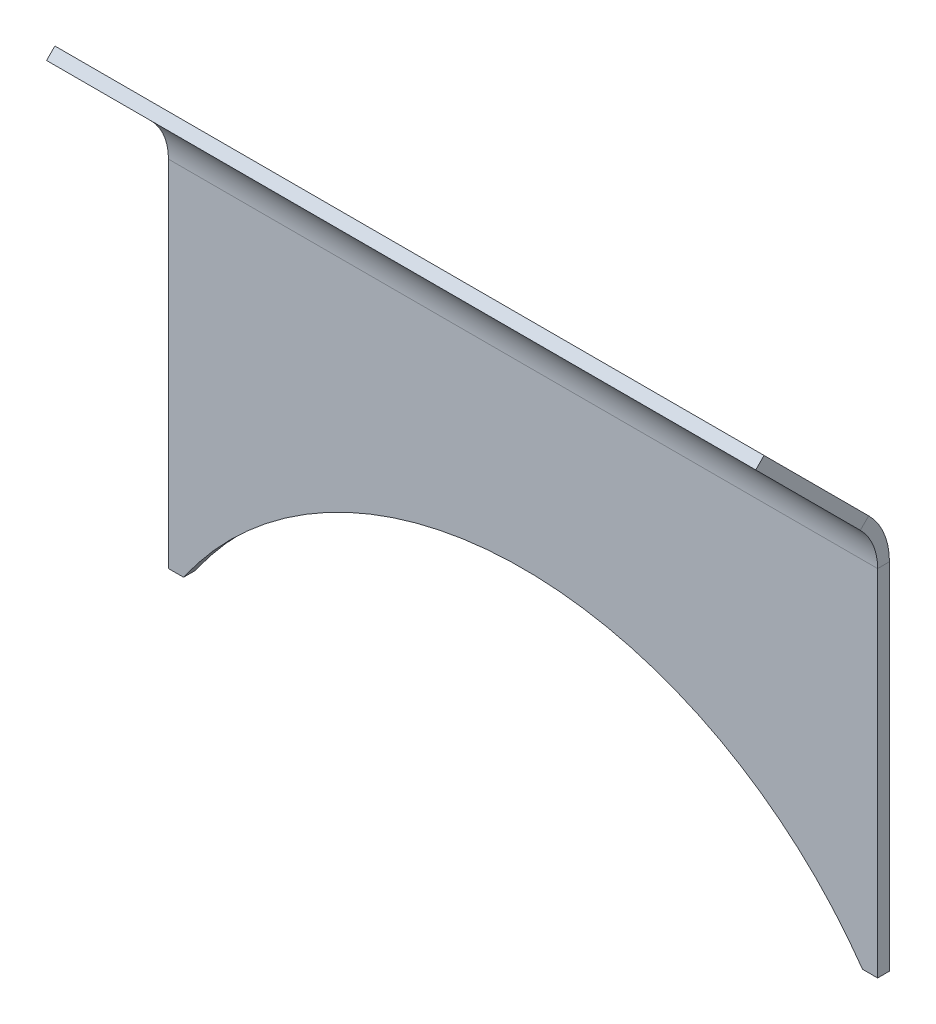
SolidWorks part; units mm, degrees
note: The reader was unsure of these and kept them because the rebuilt part matched: flange length of "Ребро-кромка1".
material "AISI 304"
ref_plane "Спереди" through (0, 0, 0) normal (0, 0, 1) x (1, 0, 0)
ref_plane "Сверху" through (0, 0, 0) normal (0, 1, 0) x (1, 0, 0)
ref_plane "Справа" through (0, 0, 0) normal (1, 0, 0) x (0, 0, -1)
sketch "Эскиз2" plane through (0, 0, 0) normal (0, 0, 1) x (1, 0, 0)
  line L5 (0, 0) -> (120, 0)
  line L6 (120, 0) -> (120, 60)
  line L8 (0, 60) -> (0, 0)
  line L9 (120, 60) -> (0, 60)
  line L10 (60, 60) -> (60, 0) construction
  dimension "D2" = 60
  dimension "D3" = 120
sketch "Эскиз3" plane through (0, 0, 0) normal (0, 0, 1) x (1, 0, 0)
  line L0 (50, 0) -> (-50, 0) construction
  line L1 (0, -50) -> (0, 50) construction
  circle A0 centre (60, -40) radius 70
  dimension "D1" = 140
  dimension "D2" = 40
  dimension "D3" = 60
base flange "Базовая кромка1" sketch "Эскиз2" thickness 2 reverse thickness direction yes parameters "D1"=10
edge flange "Ребро-кромка1" sketch "Эскиз10" flange angle 135 flange length 30 flange position bend outside bend radius 10 thickness 2 relief rectangular parameters "D6"=10
sketch "Эскиз10" plane through (0, 60, 2) normal (0, 0.7071, -0.7071) x (-1, 0, 0)
  line L0 (-120, 0) -> (0, 0) construction
  line L1 (-120, 0) -> (0, 0)
  line L2 (-120, 0) -> (-120, 29.1716)
  line L3 (-120, 29.1716) -> (0, 29.1716)
  line L4 (0, 29.1716) -> (0, 0)
bend "EdgeBend1" bend radius 10 bend angle 45 parameters "D5"=1
extrude "Вырез-Вытянуть3" cut sketch "Эскиз3" along normal up to next contours A0 normal cut yes
sketch "Сгиб-Линии1" plane through (0, 0, 0) normal (0, 1, 0) x (1, 0, 0)
sketch "Граничная рамка1" plane through (0, 0, 0) normal (0, 1, 0) x (1, 0, 0)
sheet metal parameters "Листовой металл7" thickness 2 parameters "D1"=10
flat pattern "Развертка7" [suppressed]
sketch "Сгиб-Линии2" plane through (0, 0, 0) normal (0, 1, 0) x (1, 0, 0)
sketch "Граничная рамка2" [suppressed] plane through (0, 0, 0) normal (0, 1, 0) x (1, 0, 0)
sheet metal parameters "Листовой металл8" thickness 2 parameters "D1"=10
flat pattern "Развертка7" [suppressed]
sketch "Сгиб-Линии2" plane through (0, 0, 0) normal (0, 1, 0) x (1, 0, 0)
sketch "Граничная рамка2" [suppressed] plane through (0, 0, 0) normal (0, 1, 0) x (1, 0, 0)
bend of the flat pattern "Плоское состояние-<EdgeBend1>1"
sheet metal parameters "Листовой металл9" thickness 2 parameters "D1"=10
flat pattern "Развертка7" [suppressed]
sketch "Сгиб-Линии2" plane through (0, 0, 0) normal (0, 1, 0) x (1, 0, 0)
sketch "Граничная рамка2" [suppressed] plane through (0, 0, 0) normal (0, 1, 0) x (1, 0, 0)
bend of the flat pattern "Плоское состояние-<EdgeBend1>1"
